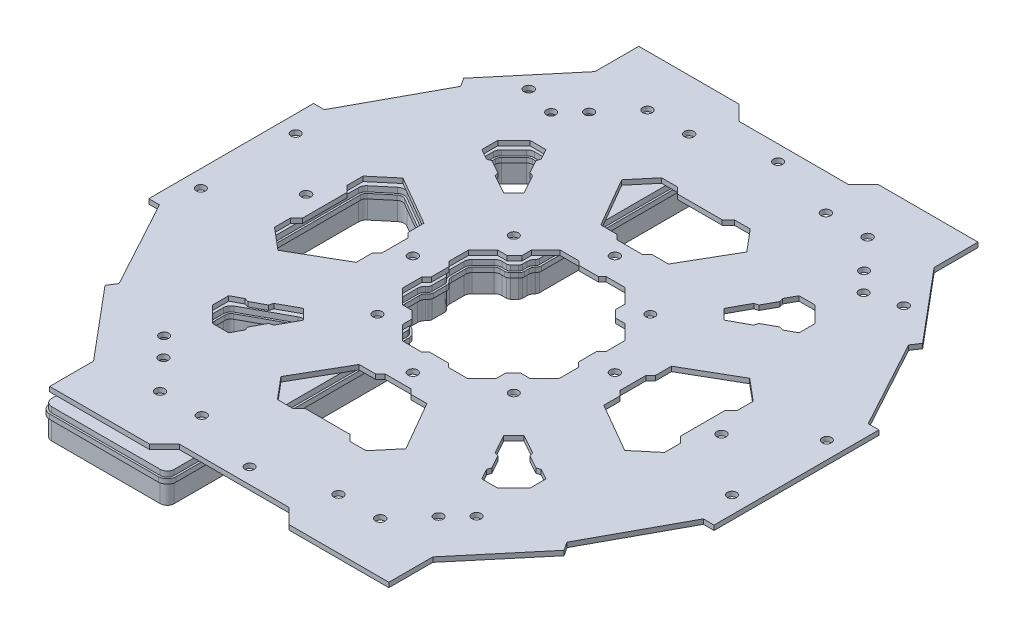
SolidWorks part; units mm, degrees
ref_plane "Front Plane" through (0, 0, 0) normal (0, 0, 1) x (1, 0, 0)
ref_plane "Top Plane" through (0, 0, 0) normal (0, 1, 0) x (1, 0, 0)
ref_plane "Right Plane" through (0, 0, 0) normal (1, 0, 0) x (0, 0, -1)
sketch "Sketch1" plane through (0, 0, 0) normal (0, 1, 0) x (1, 0, 0)
  line L0 (52.634, -248.9155) -> (166.634, -248.9155) construction
  line L1 (850, -366.6667) -> (850, -1833.3333) construction
  line L2 (-47.6733, 29.4348) -> (41.7581, 29.4348) construction
  line L3 (849.9185, -366.6667) -> (849.9185, -1833.3333) construction
  dimension "D1" = 114
sketch "Sketch3" plane through (0, 0, 0) normal (0, 1, 0) x (1, 0, 0)
  line L0 (56.1658, -87.8715) -> (161.6034, -87.8715) construction
  line L1 (56.1658, -87.8715) -> (56.1658, -218.0115) construction
  line L2 (161.6034, -87.8715) -> (161.6034, -218.4236) construction
  line L3 (56.1658, -218.0115) -> (161.6034, -218.4236) construction
  line L4 (56.5889, -217.9456) -> (56.5889, -87.8715) construction
  line L5 (56.5889, -217.9456) -> (161.6034, -217.9456) construction
  line L6 (62.8776, -224.4302) -> (62.8776, -81.3868) construction
  line L7 (62.8776, -224.4302) -> (155.3146, -224.4302) construction
  line L8 (62.8776, -81.3868) -> (155.3146, -81.3868) construction
  line L9 (155.3146, -224.4302) -> (155.3146, -81.3868) construction
  line L10 (62.8776, -81.3868) -> (155.3146, -224.4302) construction
  line L11 (62.8776, -224.4302) -> (155.3146, -81.3868) construction
  line L12 (109.0961, -152.9085) -> (109.0961, -217.9456) construction
  line L13 (56.5889, -87.8715) -> (161.6034, -87.8715) construction
  line L14 (109.0961, -241.7141) -> (109.0961, -64.103) construction
  line L15 (161.6034, -217.9456) -> (161.6034, -87.8715) construction
  line L16 (56.5889, -217.9456) -> (161.6034, -87.8715) construction
  line L17 (56.5889, -87.8715) -> (161.6034, -217.9456) construction
  line L18 (86.1682, -175.8365) -> (86.1682, -129.9806) construction
  line L19 (86.1682, -175.8365) -> (132.0241, -175.8365) construction
  line L20 (86.1682, -129.9806) -> (132.0241, -129.9806) construction
  line L21 (132.0241, -175.8365) -> (132.0241, -129.9806) construction
  line L22 (86.1682, -175.8365) -> (132.0241, -129.9806) construction
  line L23 (86.1682, -129.9806) -> (132.0241, -175.8365) construction
  line L24 (19.8431, -168.8456) -> (19.8431, -136.9715) construction
  line L25 (19.8431, -168.8456) -> (198.3491, -168.8456) construction
  line L26 (19.8431, -136.9715) -> (198.3491, -136.9715) construction
  line L27 (198.3491, -168.8456) -> (198.3491, -136.9715) construction
  line L28 (19.8431, -168.8456) -> (198.3491, -136.9715) construction
  line L29 (19.8431, -136.9715) -> (198.3491, -168.8456) construction
  line L30 (39.2916, -152.9085) -> (178.9007, -152.9085) construction
  line L31 (143.0495, -152.9085) -> (75.1427, -152.9085) construction
  line L32 (143.0495, -152.9085) -> (109.0961, -118.9552) construction
  line L33 (143.0495, -152.9085) -> (109.0961, -186.8619) construction
  line L34 (109.0961, -118.9552) -> (75.1427, -152.9085) construction
  line L35 (109.0961, -186.8619) -> (75.1427, -152.9085) construction
  line L36 (143.0495, -152.9085) -> (75.1427, -152.9085) construction
  line L37 (109.0961, -118.9552) -> (109.0961, -186.8619) construction
  line L38 (72.1037, -234.8128) -> (72.1037, -71.0043) construction
  line L39 (72.1037, -234.8128) -> (146.0885, -234.8128) construction
  line L40 (72.1037, -71.0043) -> (146.0885, -71.0043) construction
  line L41 (146.0885, -234.8128) -> (146.0885, -71.0043) construction
  line L42 (72.1037, -234.8128) -> (146.0885, -71.0043) construction
  line L43 (72.1037, -71.0043) -> (146.0885, -234.8128) construction
  line L44 (86.1271, -234.8128) -> (86.1271, -71.0043) construction
  line L45 (86.1271, -234.8128) -> (132.0652, -234.8128) construction
  line L46 (86.1271, -71.0043) -> (132.0652, -71.0043) construction
  line L47 (132.0652, -234.8128) -> (132.0652, -71.0043) construction
  line L48 (86.1271, -234.8128) -> (132.0652, -71.0043) construction
  line L49 (86.1271, -71.0043) -> (132.0652, -234.8128) construction
  line L50 (46.0681, -84.875) -> (172.1241, -84.875) construction
  circle A4 centre (155.3146, -81.3868) radius 1.55
  circle A5 centre (62.8776, -81.3868) radius 1.55
  circle A6 centre (62.8776, -224.4302) radius 1.55
  circle A7 centre (155.3146, -224.4302) radius 1.55
  circle A10 centre (56.5889, -87.8715) radius 1.55
  circle A11 centre (56.5889, -217.9456) radius 1.55
  circle A12 centre (161.6034, -87.8715) radius 1.55
  circle A13 centre (161.6034, -217.9456) radius 1.55
  circle A14 centre (132.0241, -175.8365) radius 1.55
  circle A15 centre (86.1682, -175.8365) radius 1.55
  circle A16 centre (86.1682, -129.9806) radius 1.55
  circle A17 centre (132.0241, -129.9806) radius 1.55
  circle A18 centre (19.8431, -136.9715) radius 1.55
  circle A19 centre (19.8431, -168.8456) radius 1.55
  circle A20 centre (198.3491, -136.9715) radius 1.55
  circle A21 centre (198.3491, -168.8456) radius 1.55
  circle A22 centre (178.9007, -152.9085) radius 1.59
  circle A23 centre (39.2916, -152.9085) radius 1.59
  circle A24 centre (75.1427, -152.9085) radius 1.59
  circle A25 centre (143.0495, -152.9085) radius 1.59
  circle A26 centre (109.0961, -118.9552) radius 1.59
  circle A27 centre (109.0961, -186.8619) radius 1.59
  circle A28 centre (72.1037, -71.0043) radius 1.59
  circle A29 centre (86.1271, -71.0043) radius 1.59
  circle A30 centre (132.0652, -71.0043) radius 1.59
  circle A31 centre (146.0885, -71.0043) radius 1.59
  circle A32 centre (72.1037, -234.8128) radius 1.59
  circle A33 centre (86.1271, -234.8128) radius 1.59
  circle A34 centre (132.0652, -234.8128) radius 1.59
  circle A35 centre (146.0885, -234.8128) radius 1.59
  circle A36 centre (109.0961, -64.103) radius 1.55
  circle A37 centre (109.0961, -241.7141) radius 1.55
  circle A38 centre (46.0681, -84.875) radius 1.59
  circle A39 centre (172.1241, -84.875) radius 1.59
  point P48 (109.0961, -152.9085)
  point P50 (109.0961, -152.9085)
  point P74 (109.0961, -84.875)
  point P82 (109.0961, -152.9085)
  dimension "D1" = 3.1
  dimension "D2" = 3.1
  dimension "D3" = 3.18
ref_point "Point1"
sketch "Sketch2" plane through (0, 0, 0) normal (0, 1, 0) x (1, 0, 0)
  line L0 (52.0961, -251.9085) -> (166.0961, -251.9085)
  line L1 (204.0961, -180.6085) -> (14.0961, -125.2085) construction
  line L2 (17.6961, -180.6085) -> (33.8241, -210.3126)
  line L4 (52.0961, -251.9085) -> (52.0961, -53.9085) construction
  line L5 (52.0961, -53.9085) -> (166.0961, -53.9085)
  line L6 (166.0961, -251.9085) -> (166.0961, -53.9085) construction
  line L7 (204.0961, -125.2085) -> (14.0961, -180.6085) construction
  line L8 (155.3146, -224.4302) -> (155.3146, -81.3868) construction
  line L9 (14.0961, -180.6085) -> (204.0961, -180.6085) construction
  line L10 (14.0961, -180.6085) -> (14.0961, -125.2085)
  line L11 (14.0961, -125.2085) -> (204.0961, -125.2085) construction
  line L12 (204.0961, -180.6085) -> (204.0961, -125.2085)
  line L13 (166.0961, -251.9085) -> (52.0961, -53.9085) construction
  line L14 (62.8776, -81.3868) -> (155.3146, -81.3868) construction
  line L15 (33.8241, -210.3126) -> (31.9674, -213.1717)
  line L16 (31.9674, -213.1717) -> (52.0961, -237.1602)
  line L17 (52.0961, -251.9085) -> (166.0961, -53.9085) construction
  line L18 (109.0961, -152.9085) -> (109.0961, -251.9085) construction
  line L19 (184.3682, -210.3126) -> (186.2249, -213.1717)
  line L20 (186.2249, -213.1717) -> (166.0961, -237.1602)
  line L21 (200.4961, -180.6085) -> (184.3682, -210.3126)
  line L22 (109.0961, -152.9085) -> (204.0961, -152.9085) construction
  line L23 (31.9674, -92.6454) -> (52.0961, -68.6569)
  line L24 (33.8241, -95.5045) -> (31.9674, -92.6454)
  line L25 (17.6961, -125.2085) -> (33.8241, -95.5045)
  line L26 (200.4961, -125.2085) -> (184.3682, -95.5045)
  line L27 (184.3682, -95.5045) -> (186.2249, -92.6454)
  line L29 (90.7211, -58.9085) -> (127.4711, -58.9085)
  line L30 (127.4711, -58.9085) -> (132.4711, -53.9085)
  line L31 (90.7211, -58.9085) -> (85.7211, -53.9085)
  line L32 (186.2249, -92.6454) -> (166.0961, -68.6569)
  line L33 (52.0961, -68.6569) -> (52.0961, -53.9085)
  line L35 (166.0961, -68.6569) -> (166.0961, -53.9085)
  line L36 (166.0961, -237.1602) -> (166.0961, -251.9085)
  line L37 (52.0961, -251.9085) -> (52.0961, -237.1602)
  line L38 (14.0961, -125.2085) -> (17.6961, -125.2085)
  line L39 (200.4961, -125.2085) -> (204.0961, -125.2085)
  line L40 (200.4961, -180.6085) -> (204.0961, -180.6085)
  line L41 (14.0961, -180.6085) -> (17.6961, -180.6085)
  line L42 (109.0961, -58.9085) -> (109.0961, -152.9085) construction
  line L43 (127.4711, -246.9085) -> (132.4711, -251.9085)
  line L44 (90.7211, -246.9085) -> (127.4711, -246.9085)
  line L45 (90.7211, -246.9085) -> (85.7211, -251.9085)
  point P6 (109.0961, -152.9085)
  point P7 (109.0961, -152.9085)
  point P20 (109.0961, -152.9085)
  point P23 (109.0961, -152.9085)
  point P25 (109.0961, -152.9085)
  point P37 (109.0961, -58.9085)
  point P42 (109.0961, -152.9085)
  point P43 (109.0961, -152.9085)
  dimension "D1" = 114
  dimension "D2" = 14.7483
  dimension "D3" = 190
  dimension "D4" = 55.4
  dimension "D5" = 118.5
  dimension "D6" = 33.8
  dimension "D7" = 3.6
  dimension "D8" = 198
  dimension "D9" = 140
  dimension "D10" = 118.5
  dimension "D11" = 135
  dimension "D12" = 135
  dimension "D13" = 36.75
  dimension "D14" = 46.75
extrude "Boss-Extrude1" add sketch "Sketch2" along normal blind 1.6 contours L45 L44 L43 L0 L36 L20 L19 L21 L40 L12 L39 L26 L27 L32 L35 L5 L30 L29 L31 L33 L23 L24 L25 L38 L10 L41 L2 L15 L16 L37 region at (109.0961, 0, 152.9085)
ref_plane "Plane1" through (0, -5, 0) normal (0, -1, 0) x (-1, 0, 0)
extrude "Cut-Extrude2" cut sketch "Sketch3" along normal through all and the other way through all
sketch "Sketch4" plane through (0, 0, 0) normal (0, -1, 0) x (1, 0, 0)
  line L0 (90.7211, 58.9085) -> (127.4711, 58.9085) construction
  line L1 (149.1411, 67.0766) -> (69.0512, 67.0766)
  line L2 (149.1411, 67.0766) -> (149.1411, 74.9319)
  line L3 (149.1411, 74.9319) -> (69.0512, 74.9319)
  line L4 (69.0512, 67.0766) -> (69.0512, 74.9319)
  line L5 (149.1411, 67.0766) -> (69.0512, 74.9319) construction
  line L6 (149.1411, 74.9319) -> (69.0512, 67.0766) construction
  line L7 (146.0885, 71.0043) -> (109.0961, 71.0043) construction
  circle A0 centre (146.0885, 71.0043) radius 1.59 construction
  circle A1 centre (72.1037, 71.0043) radius 1.59 construction
  circle A2 centre (86.1271, 71.0043) radius 1.59 construction
  circle A3 centre (132.0652, 71.0043) radius 1.59 construction
  circle A4 centre (72.1037, 71.0043) radius 1.59
  circle A5 centre (86.1271, 71.0043) radius 1.59
  circle A6 centre (146.0885, 71.0043) radius 1.59
  circle A7 centre (132.0652, 71.0043) radius 1.59
  point P4 (109.0961, 71.0043)
  point P8 (109.0961, 58.9085)
extrude "Boss-Extrude2" [suppressed] add sketch "Sketch4" along normal blind 2 separate body
sketch "Sketch5" plane through (0, 0, 0) normal (0, 1, 0) x (1, 0, 0)
  line L0 (113.459, -113.9063) -> (104.7332, -113.9063)
  line L1 (109.0961, -58.9085) -> (109.0961, -152.9085) construction
  line L2 (104.7332, -113.9063) -> (103.1332, -112.3063)
  line L3 (103.1332, -112.3063) -> (97.714, -112.3063)
  line L4 (97.714, -112.3063) -> (88.089, -95.6353)
  line L5 (88.089, -95.6353) -> (94.1955, -88.3579)
  line L6 (94.1955, -88.3579) -> (99.5455, -88.3579)
  line L7 (99.5455, -88.3579) -> (101.5961, -90.4085)
  line L8 (101.5961, -90.4085) -> (116.5961, -90.4085)
  line L9 (90.7211, -58.9085) -> (127.4711, -58.9085) construction
  line L10 (109.0961, -113.9063) -> (109.0961, -90.4085) construction
  line L11 (118.6467, -88.3579) -> (116.5961, -90.4085)
  line L12 (123.9967, -88.3579) -> (118.6467, -88.3579)
  line L13 (130.1032, -95.6353) -> (123.9967, -88.3579)
  line L14 (120.4782, -112.3063) -> (130.1032, -95.6353)
  line L15 (115.059, -112.3063) -> (120.4782, -112.3063)
  line L16 (113.459, -113.9063) -> (115.059, -112.3063)
  line L17 (109.0961, -152.9085) -> (39.2916, -152.9085) construction
  line L18 (204.0961, -180.6085) -> (14.0961, -125.2085) construction
  line L19 (109.0961, -191.9107) -> (109.0961, -215.4085) construction
  line L20 (113.459, -191.9107) -> (115.059, -193.5107)
  line L21 (115.059, -193.5107) -> (120.4782, -193.5107)
  line L22 (120.4782, -193.5107) -> (130.1032, -210.1817)
  line L23 (130.1032, -210.1817) -> (123.9967, -217.4591)
  line L24 (123.9967, -217.4591) -> (118.6467, -217.4591)
  line L25 (118.6467, -217.4591) -> (116.5961, -215.4085)
  line L26 (101.5961, -215.4085) -> (116.5961, -215.4085)
  line L27 (99.5455, -217.4591) -> (101.5961, -215.4085)
  line L28 (94.1955, -217.4591) -> (99.5455, -217.4591)
  line L29 (88.089, -210.1817) -> (94.1955, -217.4591)
  line L30 (97.714, -193.5107) -> (88.089, -210.1817)
  line L31 (103.1332, -193.5107) -> (97.714, -193.5107)
  line L32 (104.7332, -191.9107) -> (103.1332, -193.5107)
  line L33 (113.459, -191.9107) -> (104.7332, -191.9107)
  line L34 (109.0961, -152.9085) -> (160.1193, -101.8854) construction
  line L35 (149.0961, -152.9085) -> (109.0961, -152.9085) construction
  line L50 (109.0961, -152.9085) -> (204.0961, -152.9085) construction
  line L51 (150.6961, -164.2906) -> (167.3671, -173.9156)
  line L52 (174.6445, -167.8091) -> (174.6445, -162.4591)
  line L53 (172.5939, -160.4085) -> (172.5939, -145.4085)
  line L54 (174.6445, -143.3579) -> (174.6445, -138.0079)
  line L55 (167.3671, -131.9014) -> (150.6961, -141.5264)
  line L56 (150.6961, -146.9456) -> (149.0961, -148.5456)
  point P20 (109.0961, -152.9085)
  line B0 (71.0917, -148.5456) -> (71.0917, -157.2714)
  line B1 (71.0917, -157.2714) -> (69.4917, -158.8714)
  line B2 (69.4917, -158.8714) -> (69.4917, -164.2906)
  line B3 (69.4917, -164.2906) -> (52.8207, -173.9156)
  line B4 (52.8207, -173.9156) -> (45.5433, -167.8091)
  line B5 (45.5433, -167.8091) -> (45.5433, -162.4591)
  line B6 (45.5433, -162.4591) -> (47.5939, -160.4085)
  line B7 (47.5939, -160.4085) -> (47.5939, -145.4085)
  line B8 (71.0917, -152.9085) -> (47.5939, -152.9085) construction
  line B9 (45.5433, -143.3579) -> (47.5939, -145.4085)
  line B10 (45.5433, -138.0079) -> (45.5433, -143.3579)
  line B11 (52.8207, -131.9014) -> (45.5433, -138.0079)
  line B12 (69.4917, -141.5264) -> (52.8207, -131.9014)
  line B13 (69.4917, -146.9456) -> (69.4917, -141.5264)
  line B14 (71.0917, -148.5456) -> (69.4917, -146.9456)
  line B15 (110.0939, -152.9085) -> (110.0939, -222.7131) construction
  line B16 (149.0961, -152.9085) -> (172.5939, -152.9085) construction
  line B17 (149.0961, -148.5456) -> (150.6961, -146.9456)
  line B18 (150.6961, -146.9456) -> (150.6961, -141.5264)
  line B19 (150.6961, -141.5264) -> (167.3671, -131.9014)
  line B20 (167.3671, -131.9014) -> (174.6445, -138.0079)
  line B21 (174.6445, -138.0079) -> (174.6445, -143.3579)
  line B22 (174.6445, -143.3579) -> (172.5939, -145.4085)
  line B23 (172.5939, -160.4085) -> (172.5939, -145.4085)
  line B24 (174.6445, -162.4591) -> (172.5939, -160.4085)
  line B25 (174.6445, -167.8091) -> (174.6445, -162.4591)
  line B26 (167.3671, -173.9156) -> (174.6445, -167.8091)
  line B27 (150.6961, -164.2906) -> (167.3671, -173.9156)
  line B28 (150.6961, -158.8714) -> (150.6961, -164.2906)
  line B29 (149.0961, -157.2714) -> (150.6961, -158.8714)
  line B30 (149.0961, -148.5456) -> (149.0961, -157.2714)
  line B31 (110.0939, -152.9085) -> (59.0708, -101.8854) construction
  line B32 (110.0939, -114.9085) -> (110.0939, -152.9085) construction
  line B33 (147.1005, -148.5456) -> (147.1005, -157.2714)
  line B34 (147.1005, -157.2714) -> (148.7005, -158.8714)
  line B35 (148.7005, -158.8714) -> (148.7005, -164.2906)
  line B36 (148.7005, -164.2906) -> (165.3715, -173.9156)
  line B37 (165.3715, -173.9156) -> (172.6489, -167.8091)
  line B38 (172.6489, -167.8091) -> (172.6489, -162.4591)
  line B39 (172.6489, -162.4591) -> (170.5983, -160.4085)
  line B40 (170.5983, -160.4085) -> (170.5983, -145.4085)
  line B41 (147.1005, -152.9085) -> (170.5983, -152.9085) construction
  line B42 (172.6489, -143.3579) -> (170.5983, -145.4085)
  line B43 (172.6489, -138.0079) -> (172.6489, -143.3579)
  line B44 (165.3715, -131.9014) -> (172.6489, -138.0079)
  line B45 (148.7005, -141.5264) -> (165.3715, -131.9014)
  line B46 (148.7005, -146.9456) -> (148.7005, -141.5264)
  line B47 (147.1005, -148.5456) -> (148.7005, -146.9456)
  line B48 (108.0983, -152.9085) -> (108.0983, -222.7131) construction
  line B49 (69.0961, -152.9085) -> (45.5983, -152.9085) construction
  line B50 (69.0961, -148.5456) -> (67.4961, -146.9456)
  line B51 (67.4961, -146.9456) -> (67.4961, -141.5264)
  line B52 (67.4961, -141.5264) -> (50.8251, -131.9014)
  line B53 (50.8251, -131.9014) -> (43.5477, -138.0079)
  line B54 (43.5477, -138.0079) -> (43.5477, -143.3579)
  line B55 (43.5477, -143.3579) -> (45.5983, -145.4085)
  line B56 (45.5983, -160.4085) -> (45.5983, -145.4085)
  line B57 (43.5477, -162.4591) -> (45.5983, -160.4085)
  line B58 (43.5477, -167.8091) -> (43.5477, -162.4591)
  line B59 (50.8251, -173.9156) -> (43.5477, -167.8091)
  line B60 (67.4961, -164.2906) -> (50.8251, -173.9156)
  line B61 (67.4961, -158.8714) -> (67.4961, -164.2906)
  line B62 (69.0961, -157.2714) -> (67.4961, -158.8714)
  line B63 (69.0961, -148.5456) -> (69.0961, -157.2714)
  line B64 (108.0983, -152.9085) -> (159.1215, -101.8854) construction
  line B65 (108.0983, -114.9085) -> (108.0983, -152.9085) construction
  dimension "D1" = 31.5
  dimension "D2" = 7.5
  dimension "D3" = 135
  dimension "D4" = 135
  dimension "D5" = 130
  dimension "D6" = 5.35
  dimension "D7" = 2.9
  dimension "D8" = 110
  dimension "D9" = 19.25
  dimension "D10" = 9.5
  dimension "D11" = 135
  dimension "D12" = 1.6
  dimension "D13" = 5.4192
  dimension "D14" = 45
  dimension "D15" = 40
sketch_block_instance "Block-Sketch5-1"
sketch_block "Block3" parameters "D1"=7.5, "D2"=135, "D3"=135, "D4"=130, "D5"=5.35, "D6"=2.9, "D7"=110, "D8"=19.25, "D9"=9.5, "D10"=135, "D11"=1.6, "D12"=5.4192, "D13"=45, "D14"=38
sketch_block_instance "Block3-2"
extrude "Cut-Extrude3" cut sketch "Sketch5" along normal through all contours L0 L16 L15 L14 L13 L12 L11 L8 L7 L6 L5 L4 L3 L2 | L20 L33 L32 L31 L30 L29 L28 L27 L26 L25 L24 L23 L22 L21 | B44 B19 B18 L56 B30 B29 B28 L51 B37 B38 B39 B40 B42 B43 | L55 B44 B43 B42 B40 B39 B38 B37 B27 B26 L52 B24 L53 B22 L54 B20 | B60 B4 B5 B6 B7 B9 B10 B11 B52 B53 B54 B55 B56 B57 B58 B59 | B63 B50 B51 B52 B11 B10 B9 B7 B6 B5 B4 B60 B61 B62 region at (109.0961, 0, 100.3184) region at (109.0961, 0, 205.4987) region at (161.6049, 0, 152.9085) region at (171.8468, 0, 152.9085) region at (56.5873, 0, 152.9085) region at (46.3455, 0, 152.9085)
sketch "Sketch9" plane through (0, 0, 0) normal (0, 1, 0) x (1, 0, 0)
  line L0 (133.8461, -152.9085) -> (84.3461, -152.9085) construction
  line L1 (84.3461, -155.9085) -> (84.3461, -149.9085)
  line L2 (84.3461, -149.9085) -> (82.7661, -148.3285)
  line L3 (82.7661, -148.3285) -> (82.7661, -141.8285)
  line L4 (82.7661, -141.8285) -> (87.6661, -136.9285)
  line L5 (87.6661, -136.9285) -> (90.8661, -136.9285)
  line L6 (90.8661, -136.9285) -> (93.3661, -134.4285)
  line L7 (93.3661, -134.4285) -> (93.3661, -131.2285)
  line L8 (93.3661, -131.2285) -> (98.1661, -126.4285)
  line L9 (98.1661, -126.4285) -> (104.5861, -126.4285)
  line L10 (104.5861, -126.4285) -> (105.8861, -127.7285)
  line L11 (105.8861, -127.7285) -> (112.3061, -127.7285)
  line L12 (109.0961, -58.9085) -> (109.0961, -152.9085) construction
  line L13 (105.8861, -178.0885) -> (112.3061, -178.0885)
  line L14 (104.5861, -179.3885) -> (105.8861, -178.0885)
  line L15 (98.1661, -179.3885) -> (104.5861, -179.3885)
  line L16 (93.3661, -174.5885) -> (98.1661, -179.3885)
  line L17 (93.3661, -171.3885) -> (93.3661, -174.5885)
  line L18 (90.8661, -168.8885) -> (93.3661, -171.3885)
  line L19 (87.6661, -168.8885) -> (90.8661, -168.8885)
  line L20 (82.7661, -163.9885) -> (87.6661, -168.8885)
  line L21 (82.7661, -157.4885) -> (82.7661, -163.9885)
  line L22 (84.3461, -155.9085) -> (82.7661, -157.4885)
  line L23 (109.0961, -152.9085) -> (109.0961, -127.7285) construction
  line L24 (133.8461, -155.9085) -> (135.4261, -157.4885)
  line L25 (135.4261, -157.4885) -> (135.4261, -163.9885)
  line L26 (135.4261, -163.9885) -> (130.5261, -168.8885)
  line L27 (130.5261, -168.8885) -> (127.3261, -168.8885)
  line L28 (127.3261, -168.8885) -> (124.8261, -171.3885)
  line L29 (124.8261, -171.3885) -> (124.8261, -174.5885)
  line L30 (124.8261, -174.5885) -> (120.0261, -179.3885)
  line L31 (120.0261, -179.3885) -> (113.6061, -179.3885)
  line L32 (113.6061, -179.3885) -> (112.3061, -178.0885)
  line L33 (113.6061, -126.4285) -> (112.3061, -127.7285)
  line L34 (120.0261, -126.4285) -> (113.6061, -126.4285)
  line L35 (124.8261, -131.2285) -> (120.0261, -126.4285)
  line L36 (124.8261, -134.4285) -> (124.8261, -131.2285)
  line L37 (127.3261, -136.9285) -> (124.8261, -134.4285)
  line L38 (130.5261, -136.9285) -> (127.3261, -136.9285)
  line L39 (135.4261, -141.8285) -> (130.5261, -136.9285)
  line L40 (135.4261, -148.3285) -> (135.4261, -141.8285)
  line L41 (133.8461, -149.9085) -> (135.4261, -148.3285)
  line L42 (133.8461, -155.9085) -> (133.8461, -149.9085)
  point P38 (109.0961, -178.0885)
  dimension "D1" = 24.75
  dimension "D2" = 135
  dimension "D3" = 3
  dimension "D4" = 6.5
  dimension "D5" = 1.58
  dimension "D6" = 4.9
  dimension "D7" = 3.2
  dimension "D8" = 2.5
  dimension "D9" = 3.2
  dimension "D10" = 4.8
  dimension "D11" = 1.3
  dimension "D12" = 6.42
extrude "Cut-Extrude4" cut sketch "Sketch9" along normal through all
sketch "Sketch10" plane through (0, 0, 0) normal (0, 1, 0) x (1, 0, 0)
  line L0 (109.0961, -152.9085) -> (58.4673, -102.2797) construction
  line L1 (109.0961, -58.9085) -> (109.0961, -152.9085) construction
  line L2 (55.7652, -104.9818) -> (61.1694, -99.5776)
  line L3 (61.1694, -99.5776) -> (66.5686, -99.5941)
  line L4 (70.5863, -109.0263) -> (68.1158, -104.5081)
  line L5 (70.5863, -109.0263) -> (71.9434, -109.4239)
  line L6 (72.0291, -119.2649) -> (75.4525, -115.8415)
  line L7 (75.4525, -115.8415) -> (71.9434, -109.4239)
  line L8 (68.1158, -104.5081) -> (68.5134, -103.1509)
  line L9 (68.5134, -103.1509) -> (66.5686, -99.5941)
  line L10 (55.7652, -104.9818) -> (55.7817, -110.381)
  line L11 (59.3385, -112.3258) -> (55.7817, -110.381)
  line L12 (60.6957, -111.9282) -> (59.3385, -112.3258)
  line L13 (65.2139, -114.3987) -> (60.6957, -111.9282)
  line L14 (65.2139, -114.3987) -> (65.6115, -115.7558)
  line L15 (72.0291, -119.2649) -> (65.6115, -115.7558)
  line L16 (45.5983, -152.9085) -> (109.0961, -152.9085) construction
  line L17 (45.5983, -160.4085) -> (45.5983, -145.4085) construction
  line L18 (109.0961, -152.9085) -> (109.0961, -36.4183) construction
  line L19 (72.0291, -186.5522) -> (65.6115, -190.0612)
  line L20 (65.2139, -191.4184) -> (65.6115, -190.0612)
  line L21 (65.2139, -191.4184) -> (60.6957, -193.8889)
  line L22 (60.6957, -193.8889) -> (59.3385, -193.4912)
  line L23 (59.3385, -193.4912) -> (55.7817, -195.4361)
  line L24 (55.7652, -200.8353) -> (55.7817, -195.4361)
  line L25 (68.5134, -202.6661) -> (66.5686, -206.223)
  line L26 (68.1158, -201.309) -> (68.5134, -202.6661)
  line L27 (75.4525, -189.9756) -> (71.9434, -196.3931)
  line L28 (72.0291, -186.5522) -> (75.4525, -189.9756)
  line L29 (70.5863, -196.7908) -> (71.9434, -196.3931)
  line L30 (70.5863, -196.7908) -> (68.1158, -201.309)
  line L31 (61.1694, -206.2395) -> (66.5686, -206.223)
  line L32 (55.7652, -200.8353) -> (61.1694, -206.2395)
  line L33 (162.4271, -200.8353) -> (157.0228, -206.2395)
  line L34 (157.0228, -206.2395) -> (151.6237, -206.223)
  line L35 (147.606, -196.7908) -> (150.0765, -201.309)
  line L36 (147.606, -196.7908) -> (146.2488, -196.3931)
  line L37 (146.1632, -186.5522) -> (142.7398, -189.9756)
  line L38 (142.7398, -189.9756) -> (146.2488, -196.3931)
  line L39 (150.0765, -201.309) -> (149.6788, -202.6661)
  line L40 (149.6788, -202.6661) -> (151.6237, -206.223)
  line L41 (162.4271, -200.8353) -> (162.4105, -195.4361)
  line L42 (158.8537, -193.4912) -> (162.4105, -195.4361)
  line L43 (157.4966, -193.8889) -> (158.8537, -193.4912)
  line L44 (152.9784, -191.4184) -> (157.4966, -193.8889)
  line L45 (152.9784, -191.4184) -> (152.5807, -190.0612)
  line L46 (146.1632, -186.5522) -> (152.5807, -190.0612)
  line L47 (146.1632, -119.2649) -> (152.5807, -115.7558)
  line L48 (152.9784, -114.3987) -> (152.5807, -115.7558)
  line L49 (152.9784, -114.3987) -> (157.4966, -111.9282)
  line L50 (157.4966, -111.9282) -> (158.8537, -112.3258)
  line L51 (158.8537, -112.3258) -> (162.4105, -110.381)
  line L52 (162.4271, -104.9818) -> (162.4105, -110.381)
  line L53 (149.6788, -103.1509) -> (151.6237, -99.5941)
  line L54 (150.0765, -104.5081) -> (149.6788, -103.1509)
  line L55 (142.7398, -115.8415) -> (146.2488, -109.4239)
  line L56 (146.1632, -119.2649) -> (142.7398, -115.8415)
  line L57 (147.606, -109.0263) -> (146.2488, -109.4239)
  line L58 (147.606, -109.0263) -> (150.0765, -104.5081)
  line L59 (157.0228, -99.5776) -> (151.6237, -99.5941)
  line L60 (162.4271, -104.9818) -> (157.0228, -99.5776)
  point P8 (58.4673, -102.2797)
  point P14 (73.7408, -117.5532)
  point P39 (73.7408, -188.2639)
  point P40 (58.4673, -203.5374)
  point P69 (159.725, -203.5374)
  point P70 (144.4515, -188.2639)
  point P71 (144.4515, -117.5532)
  point P72 (159.725, -102.2797)
  dimension "D1" = 71.6
  dimension "D2" = 45
  dimension "D3" = 50
  dimension "D4" = 135
  dimension "D5" = 135
  dimension "D6" = 1
extrude "Cut-Extrude5" cut sketch "Sketch10" against normal through all and the other way through all
sketch "Sketch11" plane through (0, 0, 0) normal (0, 1, 0) x (1, 0, 0)
  line L0 (52.0961, -244.5344) -> (94.1955, -244.5344) construction
  line L1 (52.0961, -251.9085) -> (52.0961, -237.1602) construction
  line L2 (94.1955, -244.5344) -> (94.1955, -217.4591) construction
  line L3 (94.1955, -217.4591) -> (88.089, -210.1817) construction
  line L4 (88.089, -210.1817) -> (97.714, -193.5107) construction
  line L5 (97.714, -193.5107) -> (98.1661, -179.3885) construction
  line L6 (98.1661, -179.3885) -> (93.3661, -174.5885) construction
  line L7 (93.3661, -174.5885) -> (93.3661, -171.3885)
  line L8 (93.3661, -171.3885) -> (90.8661, -168.8885)
  line L9 (90.8661, -168.8885) -> (87.6661, -168.8885)
  line L10 (87.6661, -168.8885) -> (82.7661, -163.9885)
  line L11 (82.7661, -163.9885) -> (82.7661, -157.4885)
  line L12 (82.7661, -157.4885) -> (84.3461, -155.9085)
  line L13 (84.3461, -155.9085) -> (84.3461, -149.9085)
  line L14 (84.3461, -149.9085) -> (82.7661, -148.3285)
  line L15 (82.7661, -148.3285) -> (82.7661, -141.8285)
  line L16 (82.7661, -141.8285) -> (87.6661, -136.9285)
  line L17 (87.6661, -136.9285) -> (90.8661, -136.9285)
  line L18 (90.8661, -136.9285) -> (93.3661, -134.4285)
  line L19 (93.3661, -134.4285) -> (93.3661, -131.2285)
  line L20 (93.3661, -131.2285) -> (98.1661, -126.4285) construction
  line L21 (98.1661, -126.4285) -> (98.1661, -112.3063) construction
  line L22 (103.1332, -112.3063) -> (97.714, -112.3063) construction
  line L23 (98.1661, -112.3063) -> (97.714, -112.3063) construction
  line L24 (97.714, -112.3063) -> (88.089, -95.6353) construction
  line L25 (88.089, -95.6353) -> (94.1955, -88.3579) construction
  line L26 (94.1955, -88.3579) -> (94.1955, -58.9085) construction
  line L27 (90.7211, -58.9085) -> (127.4711, -58.9085) construction
  line L29 (52.0961, -53.9085) -> (52.0961, -68.6569)
  line L30 (52.0961, -68.6569) -> (31.9674, -92.6454)
  line L31 (31.9674, -92.6454) -> (52.0961, -68.6569) construction
  line L32 (31.9674, -92.6454) -> (33.8241, -95.5045)
  line L33 (33.8241, -95.5045) -> (24.0961, -113.4212)
  line L34 (17.6961, -125.2085) -> (33.8241, -95.5045) construction
  line L35 (24.0961, -113.4212) -> (24.0961, -192.3959)
  line L36 (17.6961, -180.6085) -> (33.8241, -210.3126) construction
  line L37 (24.0961, -192.3959) -> (33.8241, -210.3126)
  line L38 (33.8241, -210.3126) -> (32.1521, -213.3919)
  line L39 (31.9674, -213.1717) -> (52.0961, -237.1602) construction
  line L40 (32.1521, -213.3919) -> (52.0961, -237.1602)
  line L41 (52.0961, -237.1602) -> (52.0961, -244.5344) construction
  line L42 (14.0961, -180.6085) -> (14.0961, -125.2085) construction
  line L43 (65.2139, -114.3987) -> (65.6115, -115.7558) construction
  line L44 (60.6957, -111.9282) -> (65.2139, -114.3987) construction
  line L45 (59.3385, -112.3258) -> (60.6957, -111.9282) construction
  line L46 (55.7817, -110.381) -> (59.3385, -112.3258) construction
  line L47 (55.7652, -104.9818) -> (55.7817, -110.381) construction
  line L48 (61.1694, -99.5776) -> (55.7652, -104.9818) construction
  line L49 (66.5686, -99.5941) -> (61.1694, -99.5776) construction
  line L50 (68.5134, -103.1509) -> (66.5686, -99.5941) construction
  line L51 (68.1158, -104.5081) -> (68.5134, -103.1509) construction
  line L52 (70.5863, -109.0263) -> (68.1158, -104.5081) construction
  line L53 (71.9434, -109.4239) -> (70.5863, -109.0263) construction
  line L54 (75.4525, -115.8415) -> (71.9434, -109.4239) construction
  line L55 (72.0291, -119.2649) -> (75.4525, -115.8415) construction
  line L56 (65.6115, -115.7558) -> (72.0291, -119.2649) construction
  line L57 (43.5477, -167.8091) -> (43.5477, -162.4591) construction
  line L58 (43.5477, -162.4591) -> (45.5983, -160.4085) construction
  line L59 (45.5983, -160.4085) -> (45.5983, -145.4085) construction
  line L60 (43.5477, -143.3579) -> (45.5983, -145.4085) construction
  line L61 (43.5477, -138.0079) -> (43.5477, -143.3579) construction
  line L62 (50.8251, -131.9014) -> (43.5477, -138.0079) construction
  line L63 (67.4961, -141.5264) -> (50.8251, -131.9014) construction
  line L64 (67.4961, -146.9456) -> (67.4961, -141.5264) construction
  line L65 (69.0961, -148.5456) -> (67.4961, -146.9456) construction
  line L66 (69.0961, -148.5456) -> (69.0961, -157.2714) construction
  line L67 (69.0961, -157.2714) -> (67.4961, -158.8714) construction
  line L68 (67.4961, -158.8714) -> (67.4961, -164.2906) construction
  line L69 (67.4961, -164.2906) -> (50.8251, -173.9156) construction
  line L70 (50.8251, -173.9156) -> (43.5477, -167.8091) construction
  line L71 (55.7817, -195.4361) -> (55.7652, -200.8353) construction
  line L72 (59.3385, -193.4912) -> (55.7817, -195.4361) construction
  line L73 (60.6957, -193.8889) -> (59.3385, -193.4912) construction
  line L74 (65.2139, -191.4184) -> (60.6957, -193.8889) construction
  line L75 (65.6115, -190.0612) -> (65.2139, -191.4184) construction
  line L76 (72.0291, -186.5522) -> (65.6115, -190.0612) construction
  line L77 (75.4525, -189.9756) -> (72.0291, -186.5522) construction
  line L78 (71.9434, -196.3931) -> (75.4525, -189.9756) construction
  line L79 (55.7652, -200.8353) -> (61.1694, -206.2395) construction
  line L80 (70.5863, -196.7908) -> (71.9434, -196.3931) construction
  line L81 (68.1158, -201.309) -> (70.5863, -196.7908) construction
  line L82 (68.5134, -202.6661) -> (68.1158, -201.309) construction
  line L83 (66.5686, -206.223) -> (68.5134, -202.6661) construction
  line L84 (61.1694, -206.2395) -> (66.5686, -206.223) construction
  line L85 (65.2139, -114.3987) -> (65.6115, -115.7558)
  line L86 (60.6957, -111.9282) -> (65.2139, -114.3987)
  line L87 (59.3385, -112.3258) -> (60.6957, -111.9282)
  line L88 (55.7817, -110.381) -> (59.3385, -112.3258)
  line L89 (55.7652, -104.9818) -> (55.7817, -110.381)
  line L90 (61.1694, -99.5776) -> (55.7652, -104.9818)
  line L91 (66.5686, -99.5941) -> (61.1694, -99.5776)
  line L92 (68.5134, -103.1509) -> (66.5686, -99.5941)
  line L93 (68.1158, -104.5081) -> (68.5134, -103.1509)
  line L94 (70.5863, -109.0263) -> (68.1158, -104.5081)
  line L95 (71.9434, -109.4239) -> (70.5863, -109.0263)
  line L96 (75.4525, -115.8415) -> (71.9434, -109.4239)
  line L97 (72.0291, -119.2649) -> (75.4525, -115.8415)
  line L98 (65.6115, -115.7558) -> (72.0291, -119.2649)
  line L99 (43.5477, -167.8091) -> (43.5477, -162.4591)
  line L100 (43.5477, -162.4591) -> (45.5983, -160.4085)
  line L101 (45.5983, -160.4085) -> (45.5983, -145.4085)
  line L102 (43.5477, -143.3579) -> (45.5983, -145.4085)
  line L103 (43.5477, -138.0079) -> (43.5477, -143.3579)
  line L104 (50.8251, -131.9014) -> (43.5477, -138.0079)
  line L105 (67.4961, -141.5264) -> (50.8251, -131.9014)
  line L106 (67.4961, -146.9456) -> (67.4961, -141.5264)
  line L107 (69.0961, -148.5456) -> (67.4961, -146.9456)
  line L108 (69.0961, -148.5456) -> (69.0961, -157.2714)
  line L109 (69.0961, -157.2714) -> (67.4961, -158.8714)
  line L110 (67.4961, -158.8714) -> (67.4961, -164.2906)
  line L111 (67.4961, -164.2906) -> (50.8251, -173.9156)
  line L112 (50.8251, -173.9156) -> (43.5477, -167.8091)
  line L113 (55.7817, -195.4361) -> (55.7652, -200.8353)
  line L114 (59.3385, -193.4912) -> (55.7817, -195.4361)
  line L115 (60.6957, -193.8889) -> (59.3385, -193.4912)
  line L116 (65.2139, -191.4184) -> (60.6957, -193.8889)
  line L117 (65.6115, -190.0612) -> (65.2139, -191.4184)
  line L118 (72.0291, -186.5522) -> (65.6115, -190.0612)
  line L119 (75.4525, -189.9756) -> (72.0291, -186.5522)
  line L120 (71.9434, -196.3931) -> (75.4525, -189.9756)
  line L121 (55.7652, -200.8353) -> (61.1694, -206.2395)
  line L122 (70.5863, -196.7908) -> (71.9434, -196.3931)
  line L123 (68.1158, -201.309) -> (70.5863, -196.7908)
  line L124 (68.5134, -202.6661) -> (68.1158, -201.309)
  line L125 (66.5686, -206.223) -> (68.5134, -202.6661)
  line L126 (61.1694, -206.2395) -> (66.5686, -206.223)
  line L127 (56.5889, -217.9456) -> (62.8776, -224.4302) construction
  line L128 (59.2809, -215.3349) -> (65.5696, -221.8196)
  line L129 (53.8969, -220.5563) -> (60.1856, -227.0409)
  line L130 (56.5889, -87.8715) -> (62.8776, -81.3868) construction
  line L131 (53.8969, -85.2608) -> (60.1856, -78.7762)
  line L132 (59.2809, -90.4821) -> (65.5696, -83.9975)
  line L133 (97.714, -112.3063) -> (97.714, -126.8806) construction
  line L134 (93.3661, -131.2285) -> (97.714, -126.8806) construction
  line L135 (97.714, -193.5107) -> (97.714, -178.9364) construction
  line L136 (93.3661, -174.5885) -> (97.714, -178.9364) construction
  line L137 (86.9012, -152.9085) -> (109.0961, -152.9085) construction
  line L138 (86.9012, -175.4085) -> (41.9012, -175.4085) construction
  line L139 (86.9012, -175.4085) -> (86.9012, -130.4085) construction
  line L140 (86.9012, -130.4085) -> (41.9012, -130.4085) construction
  line L141 (41.9012, -175.4085) -> (41.9012, -130.4085) construction
  line L142 (94.5961, -57.9085) -> (86.919, -57.9085) construction
  line L143 (86.919, -57.9085) -> (86.919, -53.9085) construction
  line L144 (166.0961, -254.9085) -> (52.0961, -254.9085) construction
  line L145 (166.0961, -254.9085) -> (52.0961, -254.9085) construction
  line L146 (52.0961, -237.1602) -> (52.0961, -254.9085)
  line L147 (52.0961, -254.9085) -> (94.5961, -254.9085)
  line L148 (94.5961, -254.9085) -> (94.5961, -175.8185)
  line L149 (94.5961, -175.8185) -> (93.3661, -174.5885)
  line L150 (93.3661, -131.2285) -> (94.5961, -129.9985)
  line L151 (94.5961, -129.9985) -> (94.5961, -53.9085)
  line L153 (52.0961, -53.9085) -> (94.5961, -53.9085)
  line L154 (96.222, -53.9085) -> (93.647, -53.9085) construction
  circle A0 centre (72.1037, -234.8128) radius 1.0378 construction
  circle A1 centre (72.1037, -234.8128) radius 1.0377
  circle A3 centre (86.1037, -234.8128) radius 1.0378
  circle A4 centre (72.1037, -71.0043) radius 1.0378 construction
  circle A6 centre (72.1037, -71.0043) radius 1.0378
  circle A7 centre (86.1037, -71.0043) radius 1.2228
  circle A8 centre (75.1427, -152.9085) radius 1.59 construction
  circle A9 centre (39.2916, -152.9085) radius 1.59 construction
  circle A10 centre (75.1427, -152.9085) radius 1.59
  circle A11 centre (39.2916, -152.9085) radius 1.59
  circle A12 centre (126.0961, -95.4085) radius 1.25 construction
  circle A14 centre (126.0961, -95.4085) radius 1.25 construction
  circle A15 centre (92.2062, -95.4085) radius 1.25
  circle A16 centre (126.0961, -210.4085) radius 1.25 construction
  circle A18 centre (126.0961, -210.4085) radius 1.25 construction
  circle A19 centre (92.2062, -210.4085) radius 1.25
  circle A20 centre (46.0681, -84.875) radius 3.75
  arc A21 (59.2809, -215.3349) -> (53.8969, -220.5563) centre (56.5889, -217.9456) ccw
  arc A22 (60.1856, -227.0409) -> (65.5696, -221.8196) centre (62.8776, -224.4302) ccw
  arc A23 (53.8969, -85.2608) -> (59.2809, -90.4821) centre (56.5889, -87.8715) ccw
  arc A24 (65.5696, -83.9975) -> (60.1856, -78.7762) centre (62.8776, -81.3868) ccw
  circle A25 centre (86.9012, -175.4085) radius 1.5
  circle A26 centre (86.9012, -130.4085) radius 1.5
  circle A27 centre (92.2062, -85.4085) radius 1.25
  circle A28 centre (92.2062, -220.4086) radius 1.25
  circle A29 centre (41.9012, -175.4085) radius 1.5
  circle A30 centre (41.9012, -130.4085) radius 1.5
  arc A31 (38.7457, -250.9085) -> (36.0457, -250.9085) centre (37.3957, -250.9085) ccw construction
  arc A32 (36.0457, -250.9085) -> (38.7457, -250.9085) centre (37.3957, -250.9085) ccw construction
  arc A33 (38.7457, -250.9085) -> (36.0457, -250.9085) centre (37.3957, -250.9085) ccw
  arc A34 (36.0457, -250.9085) -> (38.7457, -250.9085) centre (37.3957, -250.9085) ccw
  arc A35 (87.7457, -250.9085) -> (85.0457, -250.9085) centre (86.3957, -250.9085) ccw construction
  arc A36 (85.0457, -250.9085) -> (87.7457, -250.9085) centre (86.3957, -250.9085) ccw construction
  arc A37 (87.7457, -250.9085) -> (85.0457, -250.9085) centre (86.3957, -250.9085) ccw
  arc A38 (85.0457, -250.9085) -> (87.7457, -250.9085) centre (86.3957, -250.9085) ccw
  arc A39 (36.0457, -192.9085) -> (38.7457, -192.9085) centre (37.3957, -192.9085) ccw construction
  arc A40 (38.7457, -192.9085) -> (36.0457, -192.9085) centre (37.3957, -192.9085) ccw construction
  arc A41 (38.7457, -192.9085) -> (36.0457, -192.9085) centre (37.3957, -192.9085) ccw
  arc A42 (36.0457, -192.9085) -> (38.7457, -192.9085) centre (37.3957, -192.9085) ccw
  arc A43 (87.7457, -192.9085) -> (85.0457, -192.9085) centre (86.3957, -192.9085) ccw construction
  arc A44 (85.0457, -192.9085) -> (87.7457, -192.9085) centre (86.3957, -192.9085) ccw construction
  arc A45 (87.7457, -192.9085) -> (85.0457, -192.9085) centre (86.3957, -192.9085) ccw
  arc A46 (85.0457, -192.9085) -> (87.7457, -192.9085) centre (86.3957, -192.9085) ccw
  arc A47 (86.919, -57.9085) -> (94.919, -57.9085) centre (90.919, -57.9085) ccw construction
  spline S0 degree 3 poles (85.4012, -130.2434) (85.4012, -130.5737) (85.4337, -130.7357) (85.5591, -131.0385) (85.652, -131.1771) (85.8826, -131.4078) (86.0221, -131.5009) (86.3229, -131.6256) (86.4873, -131.6584) (86.8134, -131.6586) (86.9772, -131.6263) (87.2799, -131.5012) (87.4177, -131.4096) (87.6512, -131.1764) (87.743, -131.0388) (87.8686, -130.7359) (87.9011, -130.5732) (87.9012, -130.244) (87.8691, -130.0823) (87.7427, -129.7775) (87.6506, -129.6401) (87.4766, -129.4663) (87.4137, -129.4147) (87.2779, -129.3239) (87.2045, -129.2847) (86.9784, -129.1911) (86.8139, -129.1585) (86.4883, -129.1585) (86.3238, -129.1912) (86.0226, -129.3158) (85.8835, -129.4085) (85.652, -129.6398) (85.5596, -129.7774) (85.4334, -130.082) (85.4012, -130.2434) (85.4012, -130.5737) (85.4337, -130.7357) knots -0.0625 -0.0625 0 0 0.0625 0.0625 0.125 0.125 0.1875 0.1875 0.25 0.25 0.3125 0.3125 0.375 0.375 0.4375 0.4375 0.5 0.5 0.5625 0.5625 0.625 0.625 0.65625 0.65625 0.6875 0.6875 0.75 0.75 0.8125 0.8125 0.875 0.875 0.9375 0.9375 1 1 1.0625 1.0625 1.125 only from (85.4012, -130.4085) to (85.4012, -130.4085) construction
  spline S1 degree 3 poles (85.4012, -175.2434) (85.4012, -175.5737) (85.4337, -175.7357) (85.5591, -176.0385) (85.652, -176.1771) (85.8826, -176.4078) (86.0221, -176.5009) (86.3229, -176.6256) (86.4873, -176.6584) (86.8134, -176.6586) (86.9772, -176.6263) (87.2799, -176.5012) (87.4177, -176.4096) (87.6512, -176.1764) (87.743, -176.0388) (87.8686, -175.7359) (87.9011, -175.5732) (87.9012, -175.244) (87.8691, -175.0823) (87.7427, -174.7775) (87.6506, -174.6401) (87.4766, -174.4663) (87.4137, -174.4147) (87.2779, -174.3239) (87.2045, -174.2847) (86.9784, -174.1911) (86.8139, -174.1585) (86.4883, -174.1585) (86.3238, -174.1912) (86.0226, -174.3158) (85.8835, -174.4085) (85.652, -174.6398) (85.5596, -174.7774) (85.4334, -175.082) (85.4012, -175.2434) (85.4012, -175.5737) (85.4337, -175.7357) knots -0.0625 -0.0625 0 0 0.0625 0.0625 0.125 0.125 0.1875 0.1875 0.25 0.25 0.3125 0.3125 0.375 0.375 0.4375 0.4375 0.5 0.5 0.5625 0.5625 0.625 0.625 0.65625 0.65625 0.6875 0.6875 0.75 0.75 0.8125 0.8125 0.875 0.875 0.9375 0.9375 1 1 1.0625 1.0625 1.125 only from (85.4012, -175.4085) to (85.4012, -175.4085) construction
  spline S2 degree 3 poles (85.4012, -130.2434) (85.4012, -130.5737) (85.4337, -130.7357) (85.5591, -131.0385) (85.652, -131.1771) (85.8826, -131.4078) (86.0221, -131.5009) (86.3229, -131.6256) (86.4873, -131.6584) (86.8134, -131.6586) (86.9772, -131.6263) (87.2799, -131.5012) (87.4177, -131.4096) (87.6512, -131.1764) (87.743, -131.0388) (87.8686, -130.7359) (87.9011, -130.5732) (87.9012, -130.244) (87.8691, -130.0823) (87.7427, -129.7775) (87.6506, -129.6401) (87.4766, -129.4663) (87.4137, -129.4147) (87.2779, -129.3239) (87.2045, -129.2847) (86.9784, -129.1911) (86.8139, -129.1585) (86.4883, -129.1585) (86.3238, -129.1912) (86.0226, -129.3158) (85.8835, -129.4085) (85.652, -129.6398) (85.5596, -129.7774) (85.4334, -130.082) (85.4012, -130.2434) (85.4012, -130.5737) (85.4337, -130.7357) knots -0.0625 -0.0625 0 0 0.0625 0.0625 0.125 0.125 0.1875 0.1875 0.25 0.25 0.3125 0.3125 0.375 0.375 0.4375 0.4375 0.5 0.5 0.5625 0.5625 0.625 0.625 0.65625 0.65625 0.6875 0.6875 0.75 0.75 0.8125 0.8125 0.875 0.875 0.9375 0.9375 1 1 1.0625 1.0625 1.125 only from (85.4012, -130.4085) to (85.4012, -130.4085) construction
  spline S3 degree 3 poles (85.4012, -175.2434) (85.4012, -175.5737) (85.4337, -175.7357) (85.5591, -176.0385) (85.652, -176.1771) (85.8826, -176.4078) (86.0221, -176.5009) (86.3229, -176.6256) (86.4873, -176.6584) (86.8134, -176.6586) (86.9772, -176.6263) (87.2799, -176.5012) (87.4177, -176.4096) (87.6512, -176.1764) (87.743, -176.0388) (87.8686, -175.7359) (87.9011, -175.5732) (87.9012, -175.244) (87.8691, -175.0823) (87.7427, -174.7775) (87.6506, -174.6401) (87.4766, -174.4663) (87.4137, -174.4147) (87.2779, -174.3239) (87.2045, -174.2847) (86.9784, -174.1911) (86.8139, -174.1585) (86.4883, -174.1585) (86.3238, -174.1912) (86.0226, -174.3158) (85.8835, -174.4085) (85.652, -174.6398) (85.5596, -174.7774) (85.4334, -175.082) (85.4012, -175.2434) (85.4012, -175.5737) (85.4337, -175.7357) knots -0.0625 -0.0625 0 0 0.0625 0.0625 0.125 0.125 0.1875 0.1875 0.25 0.25 0.3125 0.3125 0.375 0.375 0.4375 0.4375 0.5 0.5 0.5625 0.5625 0.625 0.625 0.65625 0.65625 0.6875 0.6875 0.75 0.75 0.8125 0.8125 0.875 0.875 0.9375 0.9375 1 1 1.0625 1.0625 1.125 only from (85.4012, -175.4085) to (85.4012, -175.4085) construction
  point P120 (59.7332, -221.1879)
  point P130 (59.7332, -84.6292)
  dimension "D4" = 7.5
  dimension "D7" = 3
  dimension "D1" = 10
  dimension "D2" = 7.5
  dimension "D3" = 7.5
  dimension "D5" = 45
  dimension "D6" = 45
  dimension "D8" = 42.5
extrude "Boss-Extrude3" add sketch "Sketch11" against normal blind 1.6 separate body contours L153 L29 L30 L32 L33 L35 L37 L38 L40 L146 L147 L148 L149 L7 L8 L9 L10 L11 L12 L13 L14 L15 L16 L17 L18 L19 L150 L151 A46 A45 A42 A41 A38 A37 A30 A29 L111 L112 L99 L100 L101 L102 L103 L104 L105 region at (92.4749, 0, 176.7097)
fillet "Fillet1" radius 3 6 edges at (24.0961, -0.8, 113.4212) (24.0961, -0.8, 192.3959) (94.5961, -0.8, 53.9085) (52.0961, -0.8, 53.9085) (52.0961, -0.8, 254.9085) (94.5961, -0.8, 254.9085)
sketch "Sketch12" plane through (0, 0, 0) normal (0, 1, 0) x (1, 0, 0)
  line L0 (85.7211, -53.9085) -> (89.7211, -57.9085)
  line L1 (94.5961, -57.9085) -> (86.919, -57.9085) construction
  line L2 (90.7211, -58.9085) -> (85.7211, -53.9085) construction
  line L3 (89.7211, -57.9085) -> (94.5961, -57.9085)
  line L4 (94.5961, -57.9085) -> (94.5961, -53.9085)
  line L5 (94.5961, -53.9085) -> (85.7211, -53.9085)
extrude "Cut-Extrude6" cut sketch "Sketch12" against normal through all
sketch "Sketch14" plane through (0, 0, 0) normal (0, 1, 0) x (1, 0, 0)
  line L0 (43.5477, -162.4591) -> (43.5477, -143.3579)
  line L1 (67.4961, -164.2906) -> (69.0961, -163.3669)
  line L2 (69.0961, -163.3669) -> (69.0961, -157.2714)
  line L3 (69.0961, -148.5456) -> (69.0961, -142.4502)
  line L4 (69.0961, -142.4502) -> (67.4961, -141.5264)
  line L5 (71.9434, -109.4239) -> (68.5134, -103.1509)
  line L6 (65.6115, -115.7558) -> (59.3385, -112.3258)
  line L7 (68.5134, -202.6661) -> (71.9434, -196.3931)
  line L8 (65.6115, -190.0612) -> (59.3385, -193.4912)
  line L14 (65.6115, -115.7558) -> (72.0291, -119.2649)
  line L15 (65.6115, -115.7558) -> (72.0291, -119.2649)
  line L16 (65.2139, -114.3987) -> (65.6115, -115.7558)
  line L17 (65.2139, -114.3987) -> (65.6115, -115.7558)
  line L18 (60.6957, -111.9282) -> (65.2139, -114.3987)
  line L19 (60.6957, -111.9282) -> (65.2139, -114.3987)
  line L20 (59.3385, -112.3258) -> (60.6957, -111.9282)
  line L21 (59.3385, -112.3258) -> (60.6957, -111.9282)
  line L22 (55.7817, -110.381) -> (59.3385, -112.3258)
  line L23 (55.7817, -110.381) -> (59.3385, -112.3258)
  line L24 (55.7652, -104.9818) -> (55.7817, -110.381)
  line L25 (55.7652, -104.9818) -> (55.7817, -110.381)
  line L26 (61.1694, -99.5776) -> (55.7652, -104.9818)
  line L27 (61.1694, -99.5776) -> (55.7652, -104.9818)
  line L42 (50.8251, -173.9156) -> (67.4961, -164.2906)
  line L43 (43.5477, -167.8091) -> (50.8251, -173.9156)
  line L44 (43.5477, -162.4591) -> (43.5477, -167.8091)
  line L45 (45.5983, -160.4085) -> (43.5477, -162.4591)
  line L46 (45.5983, -145.4085) -> (45.5983, -160.4085)
  line L47 (43.5477, -143.3579) -> (45.5983, -145.4085)
  line L48 (43.5477, -138.0079) -> (43.5477, -143.3579)
  line L49 (50.8251, -131.9014) -> (43.5477, -138.0079)
  line L50 (67.4961, -141.5264) -> (50.8251, -131.9014)
  line L51 (67.4961, -146.9456) -> (67.4961, -141.5264)
  line L52 (69.0961, -148.5456) -> (67.4961, -146.9456)
  line L53 (69.0961, -157.2714) -> (69.0961, -148.5456)
  line L54 (67.4961, -158.8714) -> (69.0961, -157.2714)
  line L55 (67.4961, -164.2906) -> (67.4961, -158.8714)
  line L56 (50.8251, -173.9156) -> (67.4961, -164.2906)
  line L57 (43.5477, -167.8091) -> (50.8251, -173.9156)
  line L58 (43.5477, -162.4591) -> (43.5477, -167.8091)
  line L59 (45.5983, -160.4085) -> (43.5477, -162.4591)
  line L60 (45.5983, -145.4085) -> (45.5983, -160.4085)
  line L61 (43.5477, -143.3579) -> (45.5983, -145.4085)
  line L62 (43.5477, -138.0079) -> (43.5477, -143.3579)
  line L63 (50.8251, -131.9014) -> (43.5477, -138.0079)
  line L64 (67.4961, -141.5264) -> (50.8251, -131.9014)
  line L65 (67.4961, -146.9456) -> (67.4961, -141.5264)
  line L66 (69.0961, -148.5456) -> (67.4961, -146.9456)
  line L67 (69.0961, -157.2714) -> (69.0961, -148.5456)
  line L68 (67.4961, -158.8714) -> (69.0961, -157.2714)
  line L69 (67.4961, -164.2906) -> (67.4961, -158.8714)
  line L70 (61.1694, -206.2395) -> (66.5686, -206.223)
  line L71 (61.1694, -206.2395) -> (66.5686, -206.223)
  line L72 (55.7652, -200.8353) -> (61.1694, -206.2395)
  line L73 (55.7652, -200.8353) -> (61.1694, -206.2395)
  line L74 (55.7817, -195.4361) -> (55.7652, -200.8353)
  line L75 (55.7817, -195.4361) -> (55.7652, -200.8353)
  line L76 (59.3385, -193.4912) -> (55.7817, -195.4361)
  line L77 (59.3385, -193.4912) -> (55.7817, -195.4361)
  line L78 (60.6957, -193.8889) -> (59.3385, -193.4912)
  line L79 (60.6957, -193.8889) -> (59.3385, -193.4912)
  line L80 (65.2139, -191.4184) -> (60.6957, -193.8889)
  line L81 (65.2139, -191.4184) -> (60.6957, -193.8889)
  line L82 (65.6115, -190.0612) -> (65.2139, -191.4184)
  line L83 (65.6115, -190.0612) -> (65.2139, -191.4184)
  line L107 (66.5686, -99.5941) -> (61.1694, -99.5776)
  line L108 (66.5686, -99.5941) -> (61.1694, -99.5776)
  line L109 (68.5134, -103.1509) -> (66.5686, -99.5941)
  line L110 (68.5134, -103.1509) -> (66.5686, -99.5941)
  line L111 (68.1158, -104.5081) -> (68.5134, -103.1509)
  line L112 (68.1158, -104.5081) -> (68.5134, -103.1509)
  line L113 (70.5863, -109.0263) -> (68.1158, -104.5081)
  line L114 (70.5863, -109.0263) -> (68.1158, -104.5081)
  line L115 (71.9434, -109.4239) -> (70.5863, -109.0263)
  line L116 (71.9434, -109.4239) -> (70.5863, -109.0263)
  line L117 (75.4525, -115.8415) -> (71.9434, -109.4239)
  line L118 (75.4525, -115.8415) -> (71.9434, -109.4239)
  line L119 (72.0291, -119.2649) -> (75.4525, -115.8415)
  line L120 (72.0291, -119.2649) -> (75.4525, -115.8415)
  line L121 (72.0291, -186.5522) -> (65.6115, -190.0612)
  line L122 (72.0291, -186.5522) -> (65.6115, -190.0612)
  line L123 (75.4525, -189.9756) -> (72.0291, -186.5522)
  line L124 (75.4525, -189.9756) -> (72.0291, -186.5522)
  line L125 (71.9434, -196.3931) -> (75.4525, -189.9756)
  line L126 (71.9434, -196.3931) -> (75.4525, -189.9756)
  line L127 (70.5863, -196.7908) -> (71.9434, -196.3931)
  line L128 (70.5863, -196.7908) -> (71.9434, -196.3931)
  line L129 (68.1158, -201.309) -> (70.5863, -196.7908)
  line L130 (68.1158, -201.309) -> (70.5863, -196.7908)
  line L131 (68.5134, -202.6661) -> (68.1158, -201.309)
  line L132 (68.5134, -202.6661) -> (68.1158, -201.309)
  line L133 (66.5686, -206.223) -> (68.5134, -202.6661)
  line L134 (66.5686, -206.223) -> (68.5134, -202.6661)
  dimension "D1" = 0
  dimension "D2" = 0
  dimension "D3" = 0
extrude "Cut-Extrude7" cut sketch "Sketch14" against normal through all contours L132 L7 L128 L130 | L83 L8 L79 L81 | L69 L1 L2 L68 | L66 L3 L4 L65 | L61 L0 L59 L60 | L21 L6 L17 L19 | L116 L5 L112 L114 region at (44.5319, 0, 152.9085) region at (68.3118, 0, 160.9377) region at (68.3118, 0, 144.8793) region at (69.8135, 0, 106.5143) region at (62.7019, 0, 113.6259) region at (69.8135, 0, 199.3028) region at (62.7019, 0, 192.1912)
fillet "Fillet2" radius 2 18 edges at (61.1694, -0.8, 206.2395) (55.7652, -0.8, 200.8353) (55.7817, -0.8, 195.4361) (72.0291, -0.8, 186.5522) (75.4525, -0.8, 189.9756) (66.5686, -0.8, 206.223) (50.8251, -0.8, 173.9156) (43.5477, -0.8, 167.8091) (43.5477, -0.8, 138.0079) (50.8251, -0.8, 131.9014) (55.7817, -0.8, 110.381) (55.7652, -0.8, 104.9818) (61.1694, -0.8, 99.5776) (66.5686, -0.8, 99.5941) (75.4525, -0.8, 115.8415) (72.0291, -0.8, 119.2649) (69.0961, -0.8, 142.4502) (69.0961, -0.8, 163.3669)
fillet "Fillet3" radius 2 25 edges at (85.7211, -0.8, 53.9085) (52.0961, -0.8, 68.6569) (31.9674, -0.8, 92.6454) (33.8241, -0.8, 95.5045) (33.8241, -0.8, 210.3126) (32.1521, -0.8, 213.3919) (52.0961, -0.8, 237.1602) (93.3661, -0.8, 174.5885) (93.3661, -0.8, 171.3885) (90.8661, -0.8, 168.8885) (87.6661, -0.8, 168.8885) (82.7661, -0.8, 163.9885) (82.7661, -0.8, 157.4885) (84.3461, -0.8, 155.9085) (84.3461, -0.8, 149.9085) (82.7661, -0.8, 148.3285) (82.7661, -0.8, 141.8285) (87.6661, -0.8, 136.9285) (90.8661, -0.8, 136.9285) (93.3661, -0.8, 134.4285) (93.3661, -0.8, 131.2285) (94.5961, -0.8, 129.9985) (94.5961, -0.8, 57.9085) (89.7211, -0.8, 57.9085) (94.5961, -0.8, 175.8185)
other "Move Face1" face at (86.9012, -1.6, 176.9085) face at (41.9012, -1.6, 176.9085) face at (86.9012, -1.6, 131.9085) face at (75.1427, -1.6, 154.4985) face at (41.9012, -1.6, 131.9085) face at (39.2916, -1.6, 154.4985) offset 0.5 parameters "D1"=0.5
sketch "Sketch16" plane through (0, -1.6, 0) normal (0, -1, 0) x (1, 0, 0)
  circle A0 centre (86.1037, 71.0043) radius 1.25
  circle A1 centre (72.1037, 71.0043) radius 1.25
  circle A2 centre (92.2062, 85.4085) radius 1.25
  circle A3 centre (92.2062, 95.4085) radius 1.25
  circle A4 centre (41.9012, 130.4085) radius 1.375
  circle A5 centre (86.9012, 130.4085) radius 1.375
  circle A6 centre (75.1427, 152.9085) radius 1.25
  circle A7 centre (39.2916, 152.9085) radius 1.25
  circle A8 centre (41.9012, 175.4085) radius 1.375
  circle A9 centre (86.9012, 175.4085) radius 1.375
  circle A10 centre (86.3957, 192.9085) radius 1.375
  circle A11 centre (92.2062, 210.4085) radius 1.25
  circle A12 centre (92.2062, 220.4086) radius 1.25
  circle A13 centre (37.3957, 192.9085) radius 1.375
  circle A14 centre (72.1037, 234.8128) radius 1.25
  circle A15 centre (86.1037, 234.8128) radius 1.25
  circle A16 centre (86.3957, 250.9085) radius 1.375
  circle A17 centre (37.3957, 192.9085) radius 1.375
  circle A18 centre (86.3957, 192.9085) radius 1.375
  dimension "D1" = 2.5
  dimension "D2" = 2.75
  dimension "D3" = 2.75
extrude "Cut-Extrude8" cut sketch "Sketch16" against normal through all both and the other way through all contours A16 | A15 | A12 | A14 | A13 | A8 | A10 | A9 | A6 | A7 | A4 | A5 | A1 | A0 | A2 | A3 | A11 region at (86.1037, -1.6, 71.0043) region at (72.1037, -1.6, 71.0043) region at (92.2062, -1.6, 85.4085) region at (92.2062, -1.6, 95.4085) region at (41.9012, -1.6, 130.4085) region at (86.9012, -1.6, 130.4085) region at (75.1427, -1.6, 152.9085) region at (39.2916, -1.6, 152.9085) region at (41.9012, -1.6, 175.4085) region at (86.9012, -1.6, 175.4085) region at (86.3957, -1.6, 192.9085) region at (92.2062, -1.6, 210.4085) region at (92.2062, -1.6, 220.4086) region at (37.3957, -1.6, 192.9085) region at (72.1037, -1.6, 234.8128) region at (86.1037, -1.6, 234.8128) region at (86.3957, -1.6, 250.9085)
sketch "Sketch15" plane through (0, -1.6, 0) normal (0, -1, 0) x (1, 0, 0)
  line L8 (59.7367, 214.8929) -> (66.0254, 221.3775)
  line L9 (59.7367, 214.8929) -> (66.0254, 221.3775)
  line L10 (59.7297, 227.483) -> (53.441, 220.9983)
  line L11 (59.7297, 227.483) -> (53.441, 220.9983)
  line L12 (60.1321, 206.1002) -> (55.9045, 201.8726)
  line L13 (60.1321, 206.1002) -> (55.9045, 201.8726)
  line L14 (55.0961, 54.5485) -> (84.8927, 54.5485)
  line L16 (55.0961, 54.5485) -> (84.8927, 54.5485)
  line L18 (85.8544, 54.9469) -> (88.6828, 57.7753)
  line L20 (85.8544, 54.9469) -> (88.6828, 57.7753)
  line L22 (90.5495, 58.5485) -> (92.5961, 58.5485)
  line L24 (90.5495, 58.5485) -> (92.5961, 58.5485)
  line L26 (93.9561, 59.9085) -> (93.9561, 129.1701)
  line L28 (93.9561, 59.9085) -> (93.9561, 129.1701)
  line L30 (93.5578, 130.1318) -> (93.4994, 130.1902)
  line L32 (93.5578, 130.1318) -> (93.4994, 130.1902)
  line L34 (92.7261, 132.057) -> (92.7261, 133.6001)
  line L36 (92.7261, 132.057) -> (92.7261, 133.6001)
  line L38 (92.3278, 134.5618) -> (90.9994, 135.8902)
  line L40 (92.3278, 134.5618) -> (90.9994, 135.8902)
  line L44 (65.3888, 206.8616) -> (62.0034, 206.8719)
  line L45 (65.3888, 206.8616) -> (62.0034, 206.8719)
  line L46 (75.2909, 191.5946) -> (67.6927, 205.4907)
  line L47 (75.2909, 191.5946) -> (67.6927, 205.4907)
  line L48 (73.5374, 187.1625) -> (74.8422, 188.4673)
  line L49 (73.5374, 187.1625) -> (74.8422, 188.4673)
  line L58 (56.5139, 194.312) -> (70.41, 186.7137)
  line L59 (56.5139, 194.312) -> (70.41, 186.7137)
  line L60 (55.1327, 200.0013) -> (55.1431, 196.6159)
  line L61 (55.1327, 200.0013) -> (55.1431, 196.6159)
  line L158 (90.0377, 136.2885) -> (88.4945, 136.2885)
  line L159 (90.0377, 136.2885) -> (88.4945, 136.2885)
  line L160 (69.7311, 143.6049) -> (69.7311, 162.2122)
  line L161 (52.3554, 132.0517) -> (68.4136, 141.3229)
  line L162 (43.854, 136.922) -> (49.3442, 132.3152)
  line L163 (42.9127, 166.8765) -> (42.9127, 138.9405)
  line L164 (49.3442, 173.5019) -> (43.854, 168.8951)
  line L165 (68.4136, 164.4941) -> (52.3554, 173.7653)
  line L166 (69.7311, 143.6049) -> (69.7311, 162.2122)
  line L167 (52.3554, 132.0517) -> (68.4136, 141.3229)
  line L168 (43.854, 136.922) -> (49.3442, 132.3152)
  line L169 (42.9127, 166.8765) -> (42.9127, 138.9405)
  line L170 (49.3442, 173.5019) -> (43.854, 168.8951)
  line L171 (68.4136, 164.4941) -> (52.3554, 173.7653)
  line L172 (53.441, 84.8187) -> (59.7297, 78.3341)
  line L173 (66.0254, 84.4396) -> (59.7367, 90.9242)
  line L174 (53.441, 84.8187) -> (59.7297, 78.3341)
  line L175 (66.0254, 84.4396) -> (59.7367, 90.9242)
  line L176 (86.6278, 137.0618) -> (82.8994, 140.7902)
  line L177 (86.6278, 137.0618) -> (82.8994, 140.7902)
  line L178 (82.1261, 142.657) -> (82.1261, 147.5001)
  line L179 (82.1261, 142.657) -> (82.1261, 147.5001)
  line L180 (82.8994, 149.3669) -> (83.3078, 149.7753)
  line L181 (82.8994, 149.3669) -> (83.3078, 149.7753)
  line L182 (83.7061, 150.737) -> (83.7061, 155.0801)
  line L183 (83.7061, 150.737) -> (83.7061, 155.0801)
  line L184 (83.3078, 156.0418) -> (82.8994, 156.4502)
  line L185 (83.3078, 156.0418) -> (82.8994, 156.4502)
  line L186 (55.1431, 109.2012) -> (55.1327, 105.8158)
  line L187 (55.9045, 103.9445) -> (60.1321, 99.7169)
  line L188 (62.0034, 98.9451) -> (65.3888, 98.9555)
  line L189 (67.6927, 100.3263) -> (75.2909, 114.2224)
  line L190 (74.8422, 117.3498) -> (73.5374, 118.6546)
  line L191 (70.41, 119.1033) -> (56.5139, 111.5051)
  line L192 (55.1431, 109.2012) -> (55.1327, 105.8158)
  line L193 (55.9045, 103.9445) -> (60.1321, 99.7169)
  line L194 (62.0034, 98.9451) -> (65.3888, 98.9555)
  line L195 (67.6927, 100.3263) -> (75.2909, 114.2224)
  line L196 (74.8422, 117.3498) -> (73.5374, 118.6546)
  line L197 (70.41, 119.1033) -> (56.5139, 111.5051)
  line L198 (82.1261, 158.317) -> (82.1261, 163.1601)
  line L199 (82.1261, 158.317) -> (82.1261, 163.1601)
  line L200 (82.8994, 165.0269) -> (86.6278, 168.7553)
  line L201 (82.8994, 165.0269) -> (86.6278, 168.7553)
  line L202 (88.4945, 169.5285) -> (90.0377, 169.5285)
  line L203 (88.4945, 169.5285) -> (90.0377, 169.5285)
  line L204 (90.9994, 169.9269) -> (92.3278, 171.2553)
  line L205 (90.9994, 169.9269) -> (92.3278, 171.2553)
  line L206 (92.7261, 172.217) -> (92.7261, 173.7601)
  line L207 (92.7261, 172.217) -> (92.7261, 173.7601)
  line L208 (93.4994, 175.6269) -> (93.5578, 175.6853)
  line L209 (93.4994, 175.6269) -> (93.5578, 175.6853)
  line L210 (93.9561, 176.647) -> (93.9561, 251.9085)
  line L211 (93.9561, 176.647) -> (93.9561, 251.9085)
  line L212 (91.5961, 254.2685) -> (55.0961, 254.2685)
  line L213 (91.5961, 254.2685) -> (55.0961, 254.2685)
  line L214 (52.7361, 251.9085) -> (52.7361, 237.8881)
  line L215 (52.7361, 251.9085) -> (52.7361, 237.8881)
  line L216 (52.1185, 236.1912) -> (33.5177, 214.0237)
  line L217 (52.1185, 236.1912) -> (33.5177, 214.0237)
  line L218 (33.3644, 212.5005) -> (33.8684, 211.5723)
  line L219 (33.3644, 212.5005) -> (33.8684, 211.5723)
  line L220 (33.8684, 209.0529) -> (25.0221, 192.7601)
  line L221 (33.8684, 209.0529) -> (25.0221, 192.7601)
  line L222 (24.7361, 191.634) -> (24.7361, 114.1831)
  line L223 (24.7361, 191.634) -> (24.7361, 114.1831)
  line L224 (25.0221, 113.057) -> (33.8188, 96.8556)
  line L225 (25.0221, 113.057) -> (33.8188, 96.8556)
  line L226 (33.7128, 94.158) -> (33.3101, 93.538)
  line L227 (33.7128, 94.158) -> (33.3101, 93.538)
  line L228 (33.4089, 91.9231) -> (52.1185, 69.6259)
  line L229 (33.4089, 91.9231) -> (52.1185, 69.6259)
  line L230 (52.7361, 67.9289) -> (52.7361, 56.9085)
  line L231 (52.7361, 67.9289) -> (52.7361, 56.9085)
  arc A3 (84.8927, 54.5485) -> (85.8544, 54.9469) centre (84.8927, 55.9085) ccw
  arc A5 (84.8927, 54.5485) -> (85.8544, 54.9469) centre (84.8927, 55.9085) ccw
  arc A7 (90.5495, 58.5485) -> (88.6828, 57.7753) centre (90.5495, 55.9085) ccw
  arc A9 (62.0034, 206.8719) -> (60.1321, 206.1002) centre (61.9953, 204.237) ccw
  arc A10 (62.0034, 206.8719) -> (60.1321, 206.1002) centre (61.9953, 204.237) ccw
  arc A11 (67.6927, 205.4907) -> (65.3888, 206.8616) centre (65.3807, 204.2266) ccw
  arc A12 (67.6927, 205.4907) -> (65.3888, 206.8616) centre (65.3807, 204.2266) ccw
  arc A13 (74.8422, 188.4673) -> (75.2909, 191.5946) centre (72.979, 190.3305) ccw
  arc A14 (74.8422, 188.4673) -> (75.2909, 191.5946) centre (72.979, 190.3305) ccw
  arc A15 (66.0254, 221.3775) -> (59.7297, 227.483) centre (62.8776, 224.4302) ccw
  arc A16 (66.0254, 221.3775) -> (59.7297, 227.483) centre (62.8776, 224.4302) ccw
  arc A17 (53.441, 220.9983) -> (59.7367, 214.8929) centre (56.5889, 217.9456) ccw
  arc A18 (53.441, 220.9983) -> (59.7367, 214.8929) centre (56.5889, 217.9456) ccw
  arc A27 (70.41, 186.7137) -> (73.5374, 187.1625) centre (71.6742, 189.0257) ccw
  arc A28 (70.41, 186.7137) -> (73.5374, 187.1625) centre (71.6742, 189.0257) ccw
  arc A29 (55.1431, 196.6159) -> (56.5139, 194.312) centre (57.7781, 196.6239) ccw
  arc A30 (55.1431, 196.6159) -> (56.5139, 194.312) centre (57.7781, 196.6239) ccw
  arc A31 (55.9045, 201.8726) -> (55.1327, 200.0013) centre (57.7677, 200.0094) ccw
  arc A32 (55.9045, 201.8726) -> (55.1327, 200.0013) centre (57.7677, 200.0094) ccw
  arc A59 (90.5495, 58.5485) -> (88.6828, 57.7753) centre (90.5495, 55.9085) ccw
  arc A60 (92.5961, 58.5485) -> (93.9561, 59.9085) centre (92.5961, 59.9085) ccw
  arc A61 (92.5961, 58.5485) -> (93.9561, 59.9085) centre (92.5961, 59.9085) ccw
  arc A62 (93.9561, 129.1701) -> (93.5578, 130.1318) centre (92.5961, 129.1701) ccw
  arc A63 (93.9561, 129.1701) -> (93.5578, 130.1318) centre (92.5961, 129.1701) ccw
  arc A64 (92.7261, 132.057) -> (93.4994, 130.1902) centre (95.3661, 132.057) ccw
  arc A65 (92.7261, 132.057) -> (93.4994, 130.1902) centre (95.3661, 132.057) ccw
  arc A66 (92.7261, 133.6001) -> (92.3278, 134.5618) centre (91.3661, 133.6001) ccw
  arc A67 (92.7261, 133.6001) -> (92.3278, 134.5618) centre (91.3661, 133.6001) ccw
  arc A68 (90.9994, 135.8902) -> (90.0377, 136.2885) centre (90.0377, 134.9285) ccw
  arc A69 (90.9994, 135.8902) -> (90.0377, 136.2885) centre (90.0377, 134.9285) ccw
  arc A70 (86.6278, 137.0618) -> (88.4945, 136.2885) centre (88.4945, 138.9285) ccw
  arc A71 (86.6278, 137.0618) -> (88.4945, 136.2885) centre (88.4945, 138.9285) ccw
  arc A72 (82.1261, 142.657) -> (82.8994, 140.7902) centre (84.7661, 142.657) ccw
  arc A73 (82.1261, 142.657) -> (82.8994, 140.7902) centre (84.7661, 142.657) ccw
  arc A74 (82.8994, 149.3669) -> (82.1261, 147.5001) centre (84.7661, 147.5001) ccw
  arc A75 (82.8994, 149.3669) -> (82.1261, 147.5001) centre (84.7661, 147.5001) ccw
  arc A76 (83.3078, 149.7753) -> (83.7061, 150.737) centre (82.3461, 150.737) ccw
  arc A77 (83.3078, 149.7753) -> (83.7061, 150.737) centre (82.3461, 150.737) ccw
  arc A78 (83.7061, 155.0801) -> (83.3078, 156.0418) centre (82.3461, 155.0801) ccw
  arc A79 (83.7061, 155.0801) -> (83.3078, 156.0418) centre (82.3461, 155.0801) ccw
  arc A80 (82.1261, 158.317) -> (82.8994, 156.4502) centre (84.7661, 158.317) ccw
  arc A81 (82.1261, 158.317) -> (82.8994, 156.4502) centre (84.7661, 158.317) ccw
  arc A82 (82.8994, 165.0269) -> (82.1261, 163.1601) centre (84.7661, 163.1601) ccw
  arc A83 (82.8994, 165.0269) -> (82.1261, 163.1601) centre (84.7661, 163.1601) ccw
  arc A84 (88.4945, 169.5285) -> (86.6278, 168.7553) centre (88.4945, 166.8885) ccw
  arc A85 (88.4945, 169.5285) -> (86.6278, 168.7553) centre (88.4945, 166.8885) ccw
  arc A86 (90.0377, 169.5285) -> (90.9994, 169.9269) centre (90.0377, 170.8885) ccw
  arc A87 (90.0377, 169.5285) -> (90.9994, 169.9269) centre (90.0377, 170.8885) ccw
  arc A88 (92.3278, 171.2553) -> (92.7261, 172.217) centre (91.3661, 172.217) ccw
  arc A89 (92.3278, 171.2553) -> (92.7261, 172.217) centre (91.3661, 172.217) ccw
  arc A90 (93.4994, 175.6269) -> (92.7261, 173.7601) centre (95.3661, 173.7601) ccw
  arc A91 (93.4994, 175.6269) -> (92.7261, 173.7601) centre (95.3661, 173.7601) ccw
  arc A122 (93.5578, 175.6853) -> (93.9561, 176.647) centre (92.5961, 176.647) ccw
  arc A123 (93.5578, 175.6853) -> (93.9561, 176.647) centre (92.5961, 176.647) ccw
  arc A124 (93.9561, 251.9085) -> (91.5961, 254.2685) centre (91.5961, 251.9085) ccw
  arc A125 (93.9561, 251.9085) -> (91.5961, 254.2685) centre (91.5961, 251.9085) ccw
  arc A126 (55.0961, 254.2685) -> (52.7361, 251.9085) centre (55.0961, 251.9085) ccw
  arc A127 (55.0961, 254.2685) -> (52.7361, 251.9085) centre (55.0961, 251.9085) ccw
  arc A128 (52.1185, 236.1912) -> (52.7361, 237.8881) centre (50.0961, 237.8881) ccw
  arc A129 (52.1185, 236.1912) -> (52.7361, 237.8881) centre (50.0961, 237.8881) ccw
  arc A130 (33.5177, 214.0237) -> (33.3644, 212.5005) centre (34.5595, 213.1495) ccw
  arc A131 (33.5177, 214.0237) -> (33.3644, 212.5005) centre (34.5595, 213.1495) ccw
  arc A132 (33.8684, 209.0529) -> (33.8684, 211.5723) centre (31.5483, 210.3126) ccw
  arc A133 (33.8684, 209.0529) -> (33.8684, 211.5723) centre (31.5483, 210.3126) ccw
  arc A134 (25.0221, 192.7601) -> (24.7361, 191.634) centre (27.0961, 191.634) ccw
  arc A135 (25.0221, 192.7601) -> (24.7361, 191.634) centre (27.0961, 191.634) ccw
  arc A136 (24.7361, 114.1831) -> (25.0221, 113.057) centre (27.0961, 114.1831) ccw
  arc A137 (24.7361, 114.1831) -> (25.0221, 113.057) centre (27.0961, 114.1831) ccw
  arc A138 (33.7128, 94.158) -> (33.8188, 96.8556) centre (31.4987, 95.5959) ccw
  arc A139 (33.7128, 94.158) -> (33.8188, 96.8556) centre (31.4987, 95.5959) ccw
  arc A140 (33.3101, 93.538) -> (33.4089, 91.9231) centre (34.4507, 92.7973) ccw
  arc A141 (33.3101, 93.538) -> (33.4089, 91.9231) centre (34.4507, 92.7973) ccw
  arc A142 (52.7361, 67.9289) -> (52.1185, 69.6259) centre (50.0961, 67.9289) ccw
  arc A143 (52.7361, 67.9289) -> (52.1185, 69.6259) centre (50.0961, 67.9289) ccw
  arc A144 (52.7361, 56.9085) -> (55.0961, 54.5485) centre (55.0961, 56.9085) ccw
  arc A145 (52.7361, 56.9085) -> (55.0961, 54.5485) centre (55.0961, 56.9085) ccw
  arc A163 (68.4136, 141.3229) -> (69.7311, 143.6049) centre (67.0961, 143.6049) ccw
  arc A164 (42.9127, 138.9405) -> (43.854, 136.922) centre (45.5477, 138.9405) ccw
  arc A165 (49.3442, 132.3152) -> (52.3554, 132.0517) centre (51.0379, 134.3337) ccw
  arc A166 (43.854, 168.8951) -> (42.9127, 166.8765) centre (45.5477, 166.8765) ccw
  arc A167 (52.3554, 173.7653) -> (49.3442, 173.5019) centre (51.0379, 171.4834) ccw
  arc A168 (69.7311, 162.2122) -> (68.4136, 164.4941) centre (67.0961, 162.2122) ccw
  arc A169 (68.4136, 141.3229) -> (69.7311, 143.6049) centre (67.0961, 143.6049) ccw
  arc A170 (42.9127, 138.9405) -> (43.854, 136.922) centre (45.5477, 138.9405) ccw
  arc A171 (49.3442, 132.3152) -> (52.3554, 132.0517) centre (51.0379, 134.3337) ccw
  arc A172 (43.854, 168.8951) -> (42.9127, 166.8765) centre (45.5477, 166.8765) ccw
  arc A173 (52.3554, 173.7653) -> (49.3442, 173.5019) centre (51.0379, 171.4834) ccw
  arc A174 (69.7311, 162.2122) -> (68.4136, 164.4941) centre (67.0961, 162.2122) ccw
  arc A177 (59.7297, 78.3341) -> (66.0254, 84.4396) centre (62.8776, 81.3868) ccw
  arc A178 (59.7367, 90.9242) -> (53.441, 84.8187) centre (56.5889, 87.8715) ccw
  arc A179 (59.7297, 78.3341) -> (66.0254, 84.4396) centre (62.8776, 81.3868) ccw
  arc A180 (59.7367, 90.9242) -> (53.441, 84.8187) centre (56.5889, 87.8715) ccw
  circle A187 centre (46.0681, 84.875) radius 4.385
  circle A188 centre (46.0681, 84.875) radius 4.385
  arc A191 (56.5139, 111.5051) -> (55.1431, 109.2012) centre (57.7781, 109.1931) ccw
  arc A192 (55.1327, 105.8158) -> (55.9045, 103.9445) centre (57.7677, 105.8077) ccw
  arc A193 (60.1321, 99.7169) -> (62.0034, 98.9451) centre (61.9953, 101.5801) ccw
  arc A194 (65.3888, 98.9555) -> (67.6927, 100.3263) centre (65.3807, 101.5905) ccw
  arc A195 (75.2909, 114.2224) -> (74.8422, 117.3498) centre (72.979, 115.4866) ccw
  arc A196 (73.5374, 118.6546) -> (70.41, 119.1033) centre (71.6742, 116.7914) ccw
  arc A197 (56.5139, 111.5051) -> (55.1431, 109.2012) centre (57.7781, 109.1931) ccw
  arc A198 (55.1327, 105.8158) -> (55.9045, 103.9445) centre (57.7677, 105.8077) ccw
  arc A199 (60.1321, 99.7169) -> (62.0034, 98.9451) centre (61.9953, 101.5801) ccw
  arc A200 (65.3888, 98.9555) -> (67.6927, 100.3263) centre (65.3807, 101.5905) ccw
  arc A201 (75.2909, 114.2224) -> (74.8422, 117.3498) centre (72.979, 115.4866) ccw
  arc A202 (73.5374, 118.6546) -> (70.41, 119.1033) centre (71.6742, 116.7914) ccw
  dimension "D1" = 0.64
  dimension "D2" = 0.635
  dimension "D3" = 0.635
  dimension "D4" = 0.635
  dimension "D5" = 0.635
  dimension "D6" = 0.635
  dimension "D7" = 0.635
extrude "Boss-Extrude4" add sketch "Sketch15" along normal blind 10 separate body
move or copy body "Body-Move/Copy1" bodies to move or copy 114 copy no translate (0, -3.4, 0)
